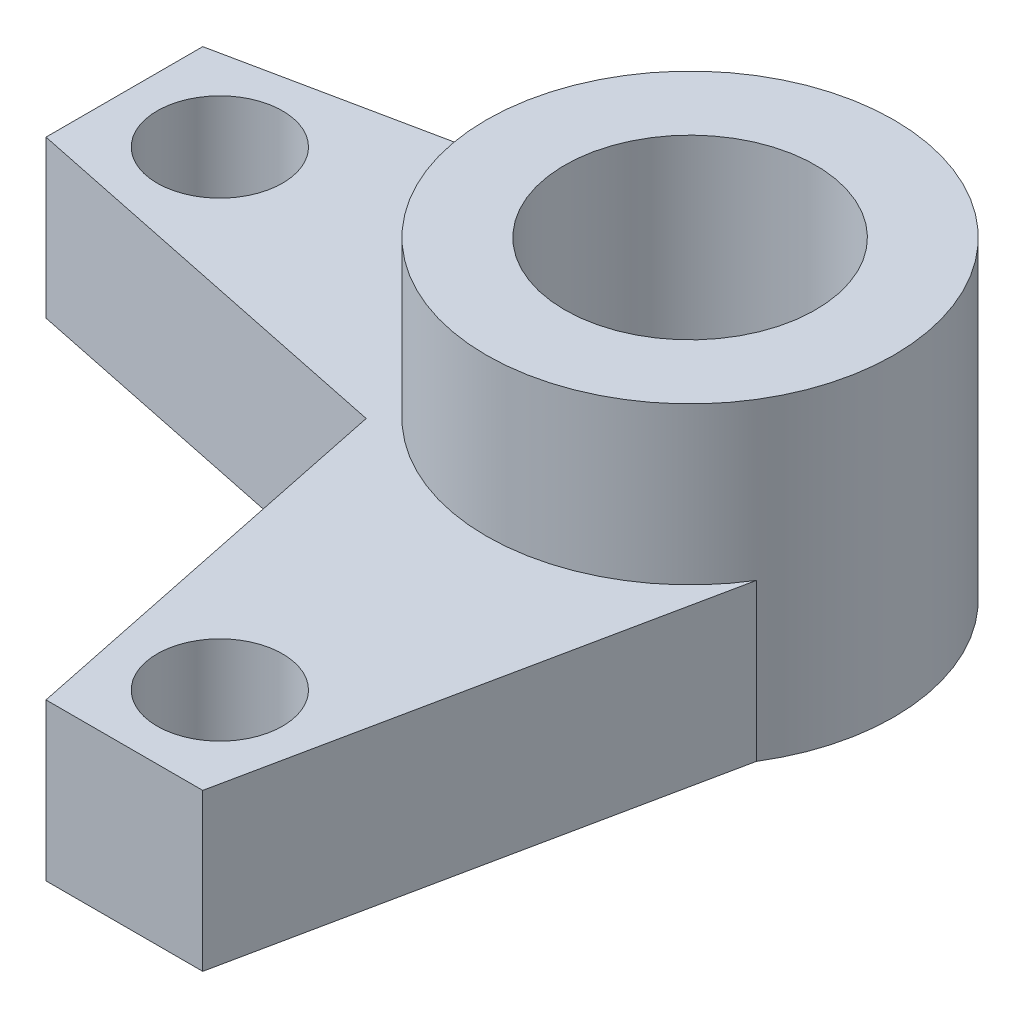
SolidWorks part; units mm, degrees
note: The reader was unsure of these and kept them because the rebuilt part matched: shared geometry of "Sketch1<3>".
ref_plane "Plan de face" through (0, 0, 0) normal (0, 0, 1) x (1, 0, 0)
ref_plane "Plan de dessus" through (0, 0, 0) normal (0, 1, 0) x (1, 0, 0)
ref_plane "Plan de droite" through (0, 0, 0) normal (1, 0, 0) x (0, 0, -1)
sketch "Sketch1" plane through (0, 0, 0) normal (0, 1, 0) x (1, 0, 0)
  line L0 (-15, 0) -> (15, 0) construction
  line L1 (-18.0461, 0) -> (18.0461, 0) construction
  line L2 (-18.0461, 2.5) -> (-18.0461, -2.5)
  line L3 (-18.0461, -2.5) -> (-3.4188, -5.5283)
  line L4 (-18.0461, 2.5) -> (-3.4188, 5.5283)
  line L5 (0, 0) -> (0, -7.2537) construction
  line L6 (-2.5, -18.0461) -> (2.5, -18.0461)
  line L7 (2.5, -18.0461) -> (5.5283, -3.4188)
  line L8 (-2.5, -18.0461) -> (-5.5283, -3.4188)
  circle A0 centre (0, 0) radius 4
  circle A1 centre (-15, 0) radius 2
  circle A3 centre (0, 0) radius 6.5
  circle A4 centre (0, -15) radius 2
  point P7 (0, 0)
  point P9 (0, 0)
  point P14 (-18.0461, 0)
  dimension "D1" = 8
  dimension "D3" = 4
  dimension "D4" = 2
  dimension "D6" = 13
  dimension "D2" = 15
  dimension "D7" = 5
extrude "Boss-Extrude1" add sketch "Sketch1" along normal blind 5
extrude "Boss-Extrude2" add sketch "Sketch1<3>" along normal blind 10 contours A3 A0
sketch "Sketch1<3>" plane through (0, 0, 0) normal (0, 1, 0) x (1, 0, 0) same geometry as "Sketch1"
